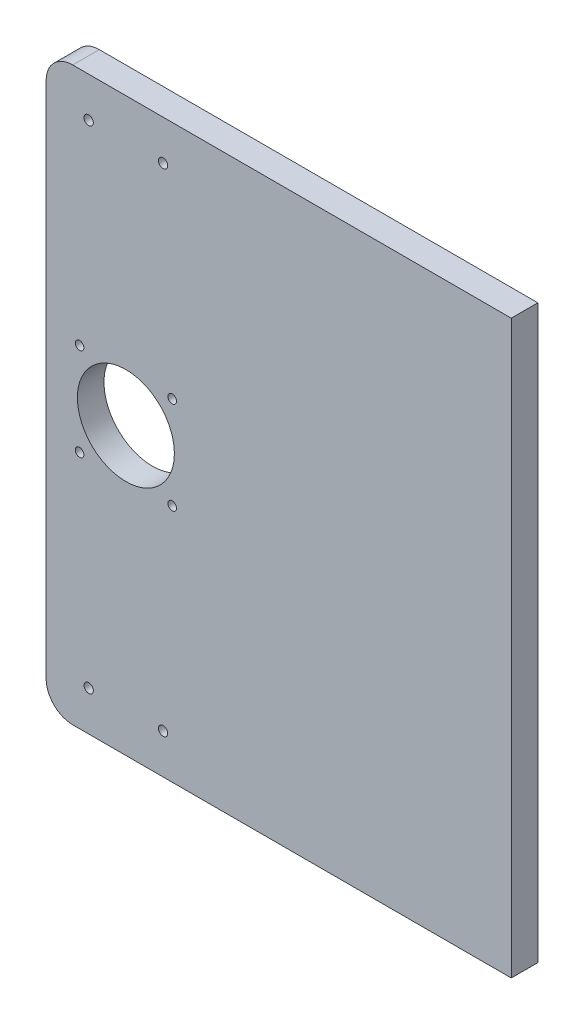
SolidWorks part; units mm, degrees
material "Органическое стекло СО-95-К ГОСТ 10667-90"
ref_plane "Спереди" through (0, 0, 0) normal (0, 0, 1) x (1, 0, 0)
ref_plane "Сверху" through (0, 0, 0) normal (0, 1, 0) x (1, 0, 0)
ref_plane "Справа" through (0, 0, 0) normal (1, 0, 0) x (0, 0, -1)
ref_axis "ОсьX" through (-88.99, 0, 0) along (1, 0, 0)
ref_axis "ОсьZ" through (0, 55, 0) along (0, -1, 0)
ref_axis "ОсьY" through (0, 0, -88.99) along (0, 0, 1)
sketch "Эскиз1" plane through (0, 0, 0) normal (0, 0, 1) x (1, 0, 0)
  line L0 (0, 0) -> (0, 59.9562) construction
  line L1 (-60, 215) -> (290, 215)
  line L2 (-60, 215) -> (-60, -215)
  line L3 (-60, -215) -> (290, -215)
  line L4 (290, 215) -> (290, -215)
  line L5 (-34.85, 34.85) -> (0, 0) construction
  line L6 (-60, 215) -> (-60, -215)
  line L7 (290, 215) -> (290, -215)
  line L8 (-109.4093, 0) -> (189.9089, 0) construction
  circle A0 centre (-28, 185) radius 3.5
  circle A16 centre (28, 185) radius 3.5
  circle A17 centre (28, -185) radius 3.5
  circle A18 centre (-28, -185) radius 3.5
  circle A19 centre (0, 0) radius 36.5
  circle A24 centre (0, 0) radius 49.2853 construction
  circle A25 centre (-34.85, 34.85) radius 3.25
  circle A26 centre (34.85, 34.85) radius 3.25
  circle A27 centre (34.85, -34.85) radius 3.25
  circle A28 centre (-34.85, -34.85) radius 3.25
  point P6 (-60, 0)
  dimension "D3" = 7
  dimension "D4" = 370
  dimension "D5" = 56
  dimension "D6" = 73
  dimension "D8" = 45
  dimension "D9" = 69.7
  dimension "D10" = 6.5
  dimension "D11" = 98.5707
  dimension "D1" = 350
  dimension "D2" = 430
  dimension "D7" = 290
extrude "Бобышка-Вытянуть1" add sketch "Эскиз1" along normal blind 20 contours L4 L1 L2 L3 A18 A16 A0 region at (118.5218, 0, 0)
fillet "Скругление2" radius 20 2 edges at (-60, -215, 10) (-60, 215, 10)
